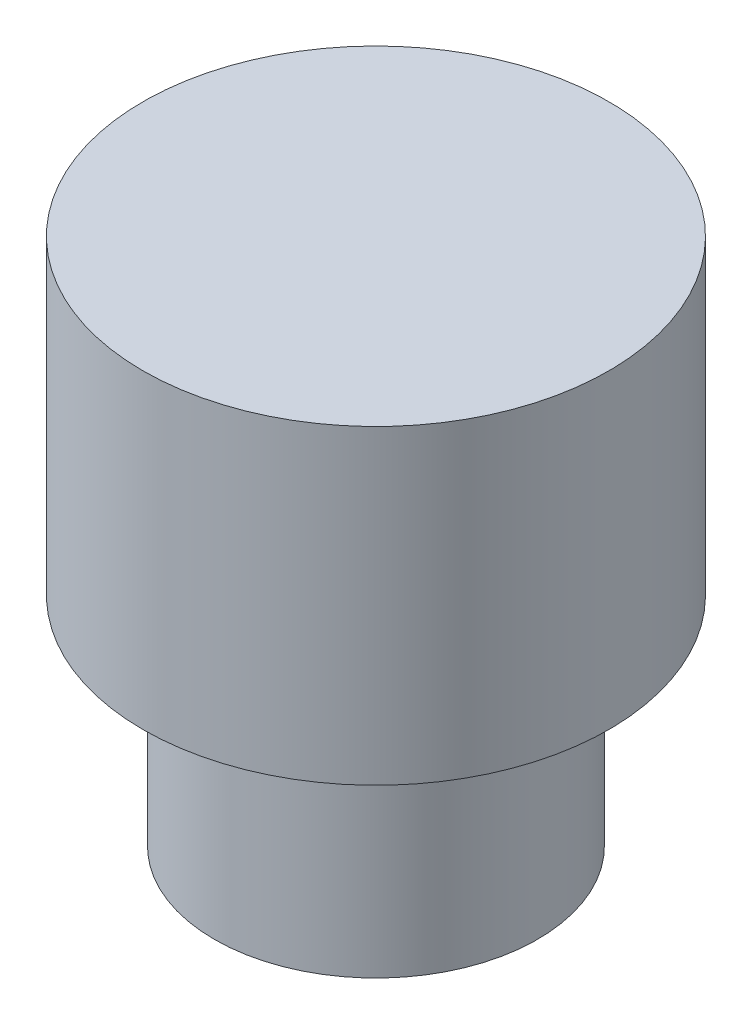
SolidWorks part; units mm, degrees
ref_plane "Front Plane" through (0, 0, 0) normal (0, 0, 1) x (1, 0, 0)
ref_plane "Top Plane" through (0, 0, 0) normal (0, 1, 0) x (1, 0, 0)
ref_plane "Right Plane" through (0, 0, 0) normal (1, 0, 0) x (0, 0, -1)
sketch "Sketch1" plane through (0, 0, 0) normal (0, 1, 0) x (1, 0, 0)
  circle A0 centre (0, 0) radius 3.2
  circle A1 centre (0, 0) radius 5.2
  dimension "D1" = 6.4
  dimension "D2" = 2
extrude "Boss-Extrude1" add sketch "Sketch1" along normal blind 7
sketch "Sketch2" plane through (0, 7, 0) normal (0, 1, 0) x (1, 0, 0)
  circle A0 centre (0, 0) radius 7.5
  dimension "D1" = 15
extrude "Boss-Extrude2" add sketch "Sketch2" along normal blind 10
sketch "Sketch3" plane through (0, 7, 0) normal (0, -1, 0) x (1, 0, 0)
  line L1 (-3.2, 0.7) -> (3.2, 0.7)
  line L2 (-3.2, 0.7) -> (-3.2, -0.7)
  line L3 (-3.2, -0.7) -> (3.2, -0.7)
  line L4 (3.2, 0.7) -> (3.2, -0.7)
  line L5 (-3.2, 0.7) -> (3.2, -0.7) construction
  line L6 (-3.2, -0.7) -> (3.2, 0.7) construction
  circle A1 centre (0, 0) radius 3.2
  circle A2 centre (0, 0) radius 3.2
  point P0 (0, 0)
  circle M5 centre (0, 0) radius 3.2
  dimension "D2" = 1.4
  dimension "D1" = 0
extrude "Boss-Extrude3" add sketch "Sketch3" along normal blind 0.8 contours L3 L1 M5 region at (0, 7, 0)
